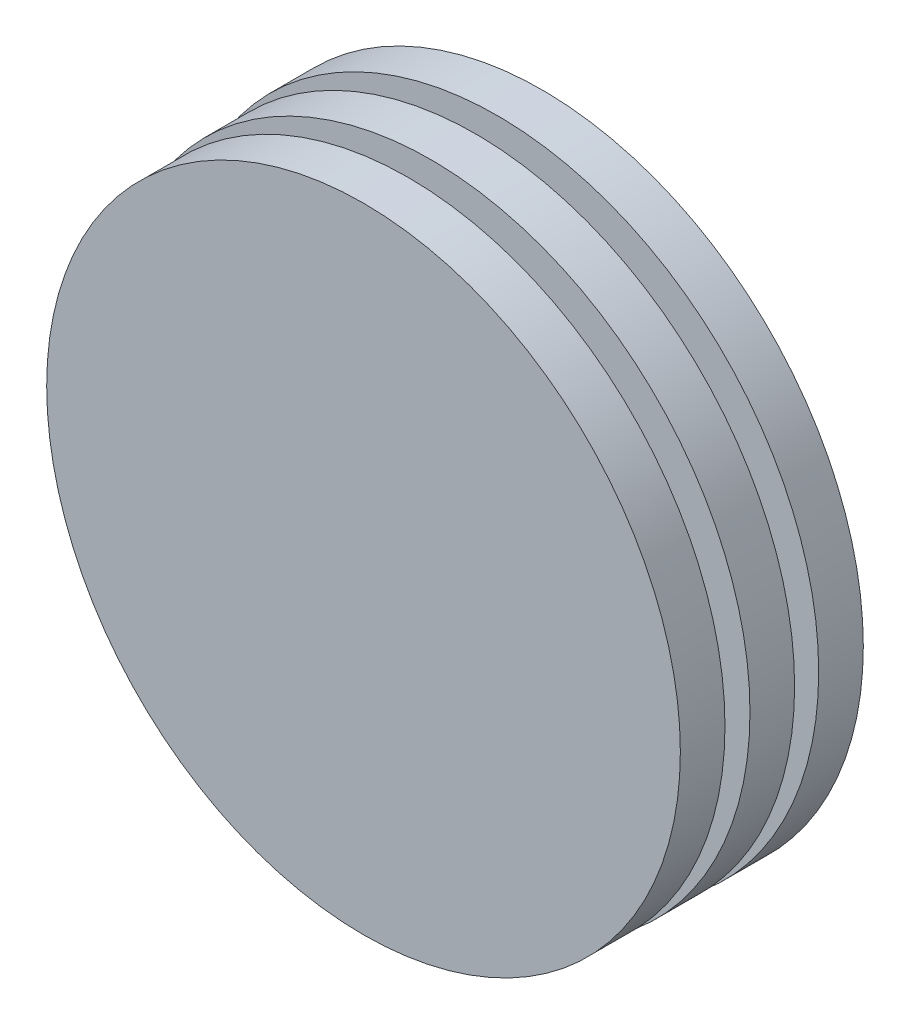
SolidWorks part; units mm, degrees
ref_plane "前基準面" through (0, 0, 0) normal (0, 0, 1) x (1, 0, 0)
ref_plane "上基準面" through (0, 0, 0) normal (0, 1, 0) x (1, 0, 0)
ref_plane "右基準面" through (0, 0, 0) normal (1, 0, 0) x (0, 0, -1)
sketch "草圖4" plane through (0, 0, 0) normal (0, 0, 1) x (1, 0, 0)
  circle A0 centre (0, 4.7204) radius 72
  circle A1 centre (0.1007, 4.2306) radius 71.5
  circle A2 centre (0, 3.7204) radius 71
  point P6 (23.003, 15.3943)
  point P7 (0, 0)
  point P8 (0, 0)
  point P9 (0, -67.2796)
  point P10 (0, 0)
  dimension "D1" = 144
  dimension "D2" = 143
  dimension "D3" = 142
extrude "填料-伸長4" add sketch "草圖4" along normal blind 10 contours A0
extrude "填料-伸長6" add sketch "草圖4<4>" along normal blind 10 from offset 15 separate body contours A1
sketch "草圖4<4>" plane through (0, 0, 0) normal (0, 0, 1) x (1, 0, 0) same geometry as "草圖4"
extrude "填料-伸長7" add sketch "草圖4<5>" along normal blind 10 from offset 30 separate body contours A2
sketch "草圖4<5>" plane through (0, 0, 0) normal (0, 0, 1) x (1, 0, 0) same geometry as "草圖4"
